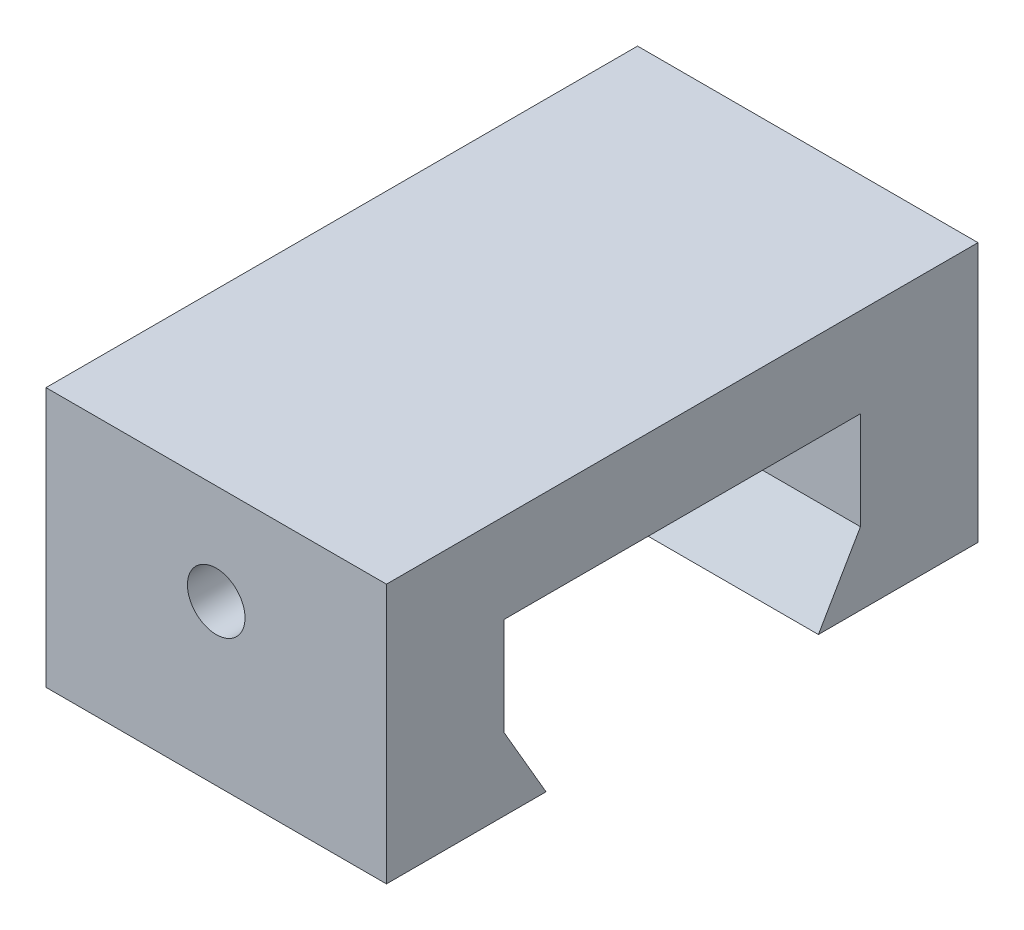
SolidWorks part; units mm, degrees
material "Delrin 2700 NC010, Low Viscosity Acetal Copolymer (SS)"
ref_plane "Front" through (0, 0, 0) normal (0, 0, 1) x (1, 0, 0)
ref_plane "Top" through (0, 0, 0) normal (0, 1, 0) x (1, 0, 0)
ref_plane "Right" through (0, 0, 0) normal (1, 0, 0) x (0, 0, -1)
ref_axis "side-side" through (80.9, 0, 0) along (-1, 0, 0)
ref_axis "up-down" through (0, 50, 0) along (0, -1, 0)
ref_axis "front-back" through (0, 0, -80.9) along (0, 0, 1)
sketch "Sketch1" plane through (0, 0, 0) normal (1, 0, 0) x (0, 0, -1)
  line L0 (-6.4, 0) -> (-8.375, 3.4)
  line L1 (-13.9, 0) -> (-6.4, 0)
  line L2 (-13.9, 0) -> (-13.9, 12.2)
  line L3 (-13.9, 12.2) -> (13.9, 12.2)
  line L4 (13.9, 0) -> (13.9, 12.2)
  line L5 (6.4, 0) -> (13.9, 0)
  line L9 (-8.375, 3.4) -> (-8.375, 8)
  line L10 (-8.375, 8) -> (8.375, 8)
  line L11 (8.375, 8) -> (8.375, 3.4)
  line L12 (8.375, 3.4) -> (6.4, 0)
  line L13 (0, 0) -> (0, 8) construction
  point P6 (-5.9924, 0)
  point P7 (5.9001, 0)
  point P8 (-8.375, 3.9588)
  point P9 (0, 0)
  point P17 (7.8822, 7.4857)
  dimension "D1" = 12.2
  dimension "D2" = 27.8
  dimension "D3" = 16.75
  dimension "D4" = 8
  dimension "D5" = 12.8
  dimension "D6" = 3.4
extrude "Boss-Extrude1" add sketch "Sketch1" along normal mid plane 16
hole_wizard "#6-32 Tapped Hole1" positions "Sketch3" profile "Sketch4" tap size "#6-32" standard "ANSI Inch" end condition through all
sketch "Sketch3" plane through (0, 0, 13.9) normal (0, 0, 1) x (1, 0, 0)
  line L0 (0, -50) -> (0, 50) construction
  line L1 (8, 0) -> (-8, 0) construction
  point P0 (0, 7.5)
  point P2 (0, 0)
  dimension "D1" = 7.5
sketch "Sketch4" plane through (0, 7.5, 13.9) normal (1, 0, 0) x (0, -1, 0)
  line L0 (0, 0) -> (0, 27.8)
  line L1 (0, 27.8) -> (1.3525, 27.8)
  line L2 (1.3525, 27.8) -> (1.3525, 0)
  line L5 (1.3525, 0) -> (0, 0)
  line L11 (0, -6.35) -> (0, 107.95) construction
  dimension "Thread Major Dia." = 2.7051
  dimension "Thru Tap Drill Depth" = 27.8
